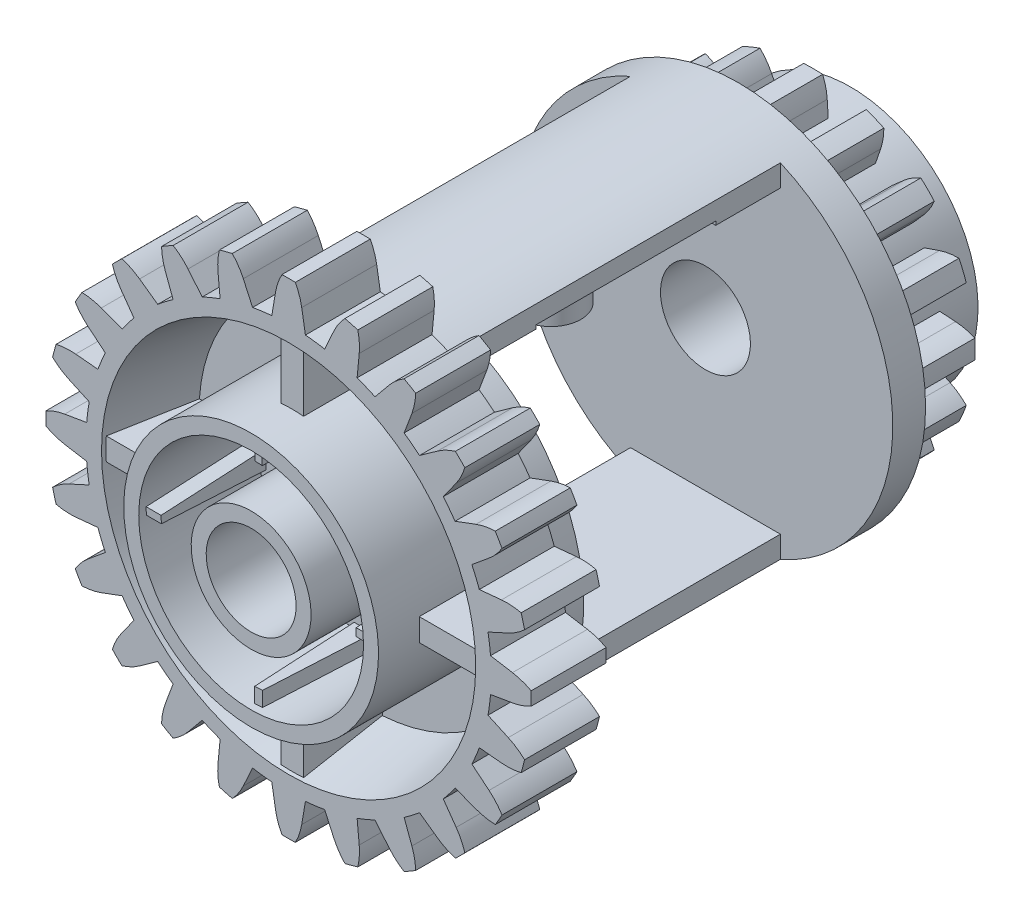
SolidWorks part; units mm, degrees
material "ABS"
ref_plane "Front Plane" through (0, 0, 0) normal (0, 0, 1) x (1, 0, 0)
ref_plane "Top Plane" through (0, 0, 0) normal (0, 1, 0) x (1, 0, 0)
ref_plane "Right Plane" through (0, 0, 0) normal (1, 0, 0) x (0, 0, -1)
sketch "Sketch2" plane through (0, 0, 0) normal (1, 0, 0) x (0, 0, -1)
  line L3 (16, 6) -> (9.9998, 6)
  line L4 (-9.6, 6) -> (-16, 6)
  line L5 (5.0474, 0) -> (-5.0474, 0) construction
  line L6 (-10, 10) -> (-10, 12.95)
  line L8 (-10, 12.95) -> (-14, 12.95)
  line L10 (-16, 6.8) -> (-9.6, 6.8)
  line L11 (-9.6, 6.8) -> (-9.6, 9.1812)
  line L12 (-9.6, 9.1812) -> (-14, 9.9863)
  line L13 (9.9997, 8.65) -> (13.9997, 8.65)
  line L14 (13.9997, 8.65) -> (13.9997, 6.8)
  line L15 (9.9997, 8.65) -> (9.9996, 10)
  line L231 (9.9996, 10) -> (-10, 10)
  line L245 (16, 6.8) -> (13.9997, 6.8)
  line L249 (16, 6) -> (16, 6.8)
  line L259 (9.9999, 3.2) -> (9.9998, 6)
  line L261 (16, 3.2) -> (9.9999, 3.2)
  line L265 (16, 2.4) -> (16, 3.2)
  line L267 (8.25, 2.4) -> (16, 2.4)
  line L270 (8.25, 8) -> (8.25, 2.4)
  line L271 (-8.25, 8) -> (8.25, 8)
  line L295 (-8.25, 2.4) -> (-8.25, 8)
  line L298 (-16, 2.4) -> (-8.25, 2.4)
  line L300 (-16, 3.2) -> (-16, 2.4)
  line L304 (-9.6, 3.2) -> (-16, 3.2)
  line L306 (-9.6, 6) -> (-9.6, 3.2)
  line L316 (-16, 6.8) -> (-16, 6)
  line L323 (-14, 12.95) -> (-14, 9.9863)
  point P10 (0, 0)
  dimension "D2" = 0.8
  dimension "D3" = 10
  dimension "D4" = 12.95
  dimension "D5" = 0.8
  dimension "D6" = 8.65
  dimension "D7" = 4
  dimension "D1" = 14
  dimension "D8" = 4
  dimension "D9" = 8
  dimension "D10" = 8.25
  dimension "D11" = 8.25
  dimension "D12" = 9.6
  dimension "D13" = 10
  dimension "D14" = 16
  dimension "D15" = 16
  dimension "D16" = 6.8
  dimension "D17" = 2.4
revolve "Revolve1" add sketch "Sketch2" angle 180 about L5 reverse direction yes
sketch "Sketch3" plane through (0, 0, 0) normal (0, 1, 0) x (1, 0, 0)
  line L0 (0, 9.9996) -> (0, -10) construction
  line L1 (4, -8.25) -> (4, 8.25)
  line L2 (4, 8.25) -> (10, 8.25)
  line L3 (10, 8.25) -> (10, -8.25)
  line L4 (10, -8.25) -> (4, -8.25)
  line L5 (0, 8.25) -> (8, 8.25) construction
  line L6 (8, -8.25) -> (0, -8.25) construction
  line L7 (10, -10) -> (10, 9.9996) construction
  dimension "D1" = 4
extrude "Cut-Extrude2" cut sketch "Sketch3" against normal through all both and the other way through all
sketch "Sketch5" plane through (0, 0, 0) normal (1, 0, 0) x (0, 0, -1)
  line L0 (-8.25, 8) -> (8.25, 8) construction
  line L1 (-8.25, 8) -> (8.25, 8)
  line L2 (8.25, 8) -> (8.25, 2.4) construction
  line L3 (8.25, 8) -> (8.25, -8)
  line L4 (-8.25, 2.4) -> (-8.25, 8) construction
  line L5 (-8.25, -8) -> (-8.25, 8)
  line L6 (-8.25, -8) -> (8.25, -8) construction
  line L7 (-8.25, -8) -> (8.25, -8)
  line L8 (4.8, 8) -> (4.8, 8.2)
  line L9 (4.8, 8.2) -> (-4.8, 8.2)
  line L10 (-4.8, 8.2) -> (-4.8, 8)
  point P9 (0, 8.2)
  dimension "D1" = 9.6
  dimension "D2" = 0.2
extrude "Cut-Extrude3" cut sketch "Sketch5" along normal through all contours L7 | L5 L7 L3 L1 | L9 L10 L1 L8 region at (0, 0, 0) region at (0, 8.1, 0)
mirror "Mirror1" about plane through (0, 0, 0) normal (1, 0, 0) of bodies 105
sketch "Sketch7" plane through (0, 0, 14) normal (0, 0, 1) x (1, 0, 0)
  line L3 (0.8968, 10.7778) -> (0.7, 11.95)
  line L5 (2.4167, 11.724) -> (1.9232, 10.6426)
  line L6 (0.8968, 10.7778) -> (1.9232, 10.6426) construction
  circle A0 centre (0, 0) radius 12.95 construction
  arc A1 (3.0052, 12.5965) -> (0.3575, 12.9451) centre (0, 0) ccw
  arc A2 (1.9232, 10.6426) -> (0.8968, 10.7778) centre (0, 0) ccw
  arc A3 (0.7, 11.95) -> (0.3575, 12.9451) centre (-2.4558, 11.4201) ccw
  arc A4 (2.4167, 11.724) -> (3.0052, 12.5965) centre (5.3279, 10.3954) cw
  dimension "D1" = 3.2
  dimension "D2" = 3.2
extrude "Cut-Extrude5" cut sketch "Sketch7" against normal up to surface (4 mm away) up to face at (0, -12.95, 10)
pattern_circular "CirPattern1" count 24 over 360 about axis through (0, 0, -5.0474) along (0, 0, 1) of "Cut-Extrude5"
sketch "Sketch8" plane through (0, 0, -13.9997) normal (0, 0, -1) x (-1, 0, 0)
  line L1 (-0.75, 7.6) -> (-0.8039, 6.7523)
  line L3 (-2.2155, 7.3085) -> (-1.8413, 6.546)
  circle A0 centre (0, 0) radius 6.8 construction
  arc A1 (-0.8039, 6.7523) -> (-1.8413, 6.546) centre (0, 0) ccw
  circle A2 centre (0, 0) radius 8.65 construction
  arc A3 (-0.5072, 8.6351) -> (-2.8359, 8.1719) centre (0, 0) ccw
  arc A4 (-2.2155, 7.3085) -> (-2.8359, 8.1719) centre (-5.0882, 5.8987) ccw
  arc A5 (-0.75, 7.6) -> (-0.5072, 8.6351) centre (2.4435, 7.3969) cw
  dimension "D1" = 3.2
  dimension "D2" = 3.2
extrude "Cut-Extrude6" cut sketch "Sketch8" against normal up to surface (3.9999 mm away) up to face at (0, -10, -9.9996)
pattern_circular "CirPattern2" count 16 over 360 about axis through (0, 0, -5.0474) along (0, 0, 1) of "Cut-Extrude6"
sketch "Sketch9" plane through (0, 8, 0) normal (0, -1, 0) x (1, 0, 0)
  circle A0 centre (0, 0) radius 1.6
  dimension "D1" = 3.2
extrude "Boss-Extrude1" add sketch "Sketch9" along normal blind 3.15 and the other way up to next
sketch "Sketch10" plane through (0, 0, 9.6) normal (0, 0, 1) x (1, 0, 0)
  line L1 (9.9683, 0.6) -> (6.7734, 0.6008)
  line L3 (9.9683, -0.6) -> (6.7734, -0.6008)
  circle A0 centre (0, 0) radius 9.9863 construction
  arc A1 (9.9683, -0.6) -> (9.9683, 0.6) centre (0, 0) ccw
  circle A2 centre (0, 0) radius 6.8 construction
  arc A3 (6.7734, -0.6008) -> (6.7734, 0.6008) centre (0, 0) ccw
  circle A4 centre (0, 0) radius 6.8 construction
extrude "Boss-Extrude2" add sketch "Sketch10" along normal offset from surface (4.2 mm away) 0.2 up to face at (0, -9.9863, 14)
ref_plane "Plane1" through (5.2, 0, 0) normal (1, 0, 0) x (0, 0, -1)
sketch "Sketch11" plane through (5.2, 0, 0) normal (1, 0, 0) x (0, 0, -1)
  line L0 (-15.6, 0) -> (15.6, 0) construction
  line L1 (-15.608, -0.1998) -> (-10, -0.5)
  line L3 (-15.608, -0.1998) -> (-15.5919, 0.1998)
  line L4 (-10, -10) -> (-10, 10) construction
  line L5 (-15.5919, 0.1998) -> (-10, 0.5)
  line L7 (-10, -0.5) -> (-10, 0.5)
  line L9 (10, 0.5) -> (15.6, 0.2)
  line L11 (10, -0.5) -> (10, 0.5)
  line L13 (15.6, -0.2) -> (10, -0.5)
  line L15 (15.6, 0.2) -> (15.6, -0.2)
  point P12 (0, 0)
  point P18 (10, 0)
  point P21 (-10, 0)
  point P22 (-15.6, 0)
  dimension "D2" = 1
  dimension "D3" = 0.4
extrude "Boss-Extrude3" add sketch "Sketch11" along normal blind 1.2
pattern_circular "CirPattern3" count 4 over 360 about axis through (0, 0, -5.0474) along (0, 0, 1) of "Boss-Extrude2", "Boss-Extrude3"
sketch "Sketch12" plane through (0, 0, 16) normal (0, 0, 1) x (1, 0, 0)
  circle A0 centre (0, 0) radius 12 construction
  dimension "D1" = 24
equation "\"D2@Sketch8\"=\"D1@Sketch8\""
